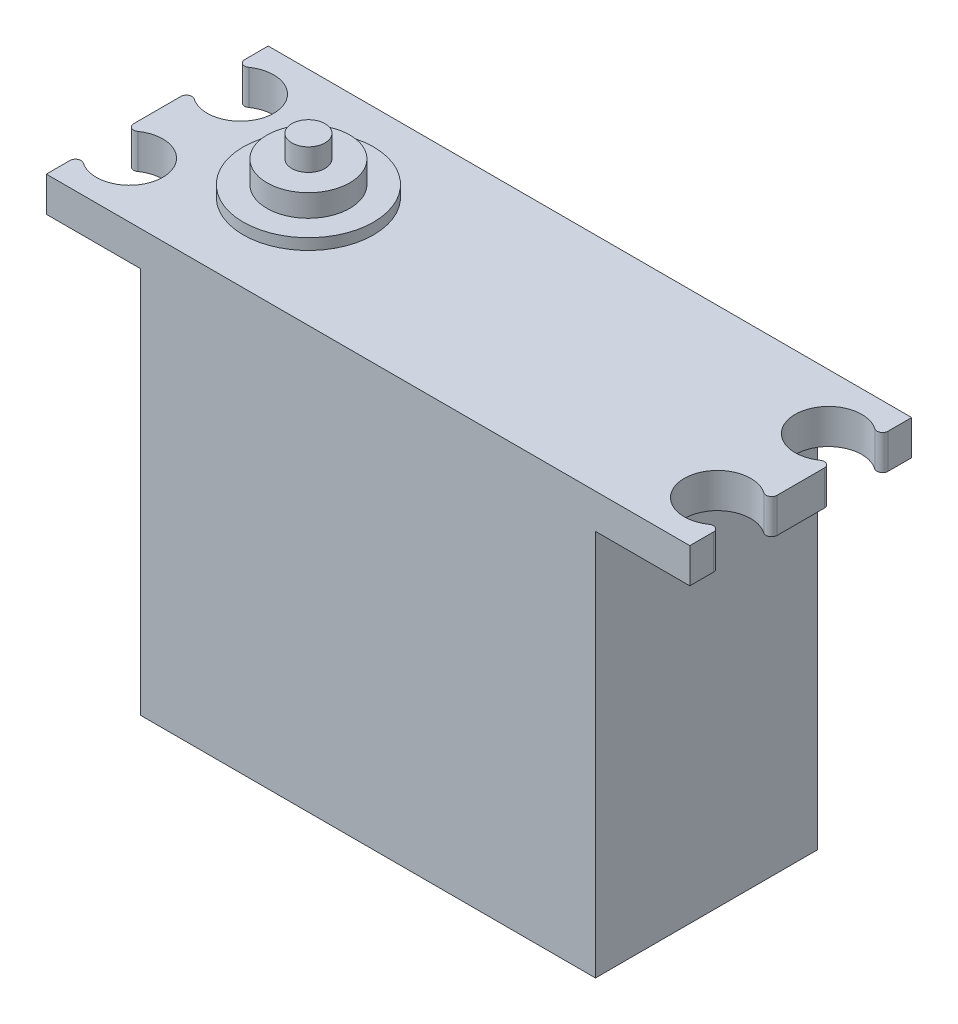
SolidWorks part; units mm, degrees
ref_plane "Front Plane" through (0, 0, 0) normal (0, 0, 1) x (1, 0, 0)
ref_plane "Top Plane" through (0, 0, 0) normal (0, 1, 0) x (1, 0, 0)
ref_plane "Right Plane" through (0, 0, 0) normal (1, 0, 0) x (0, 0, -1)
sketch "Sketch1" plane through (0, 0, 0) normal (0, 0, 1) x (1, 0, 0)
  line L0 (-29, 19) -> (29, 19)
  line L1 (20.5, -19) -> (-20.5, -19)
  line L2 (20.5, -19) -> (20.5, 15.8627)
  line L3 (20.5, 19) -> (-20.5, 19)
  line L4 (-20.5, -19) -> (-20.5, 15.8627)
  line L7 (-20.5, 15.8627) -> (-29, 15.8627)
  line L8 (29, 19) -> (29, 15.8627)
  line L9 (29, 15.8627) -> (20.5, 15.8627)
  line L10 (-29, 19) -> (-29, 15.8627)
  point P0 (0, 0)
  point P6 (0, 19)
  dimension "D1" = 41
  dimension "D2" = 38
extrude "Boss-Extrude1" add sketch "Sketch1" against normal blind 20 contours L0 L8 L9 L2 L1 L4 L7 L10
sketch "Sketch2" plane through (0, 19, 0) normal (0, 1, 0) x (1, 0, 0)
  line L0 (-29, 10) -> (31.146, 10) construction
  line L1 (-29, 20) -> (-29, 0) construction
  line L2 (0, 0) -> (0, 20) construction
  line L3 (-29, 0) -> (29, 0) construction
  line L4 (-29, 20) -> (29, 20) construction
  line L5 (29, 20) -> (29, 0) construction
  circle A0 centre (26.5, 5) radius 3
  circle A1 centre (26.5, 15) radius 3
  circle A2 centre (-26.5, 5) radius 3
  circle A3 centre (-26.5, 15) radius 3
  dimension "D1" = 6
  dimension "D2" = 2.5
  dimension "D3" = 10
extrude "Cut-Extrude2" cut sketch "Sketch2" against normal through all
fillet "Fillet1" radius 0.5 8 edges at (-29, 17.4314, -16.6583) (-29, 17.4314, -13.3417) (-29, 17.4314, -6.6583) (-29, 17.4314, -3.3417) (29, 17.4314, -13.3417) (29, 17.4314, -16.6583) (29, 17.4314, -6.6583) (29, 17.4314, -3.3417)
sketch "Sketch4" plane through (0, 19, 0) normal (0, 1, 0) x (1, 0, 0)
  line L0 (-29, 10) -> (29, 10) construction
  line L1 (-29, 12.1277) -> (-29, 7.8723) construction
  line L2 (29, 12.1277) -> (29, 7.8723) construction
  circle A0 centre (-15.3758, 10) radius 5.8721
extrude "Boss-Extrude2" add sketch "Sketch4" along normal blind 1
sketch "Sketch5" plane through (0, 20, 0) normal (0, 1, 0) x (1, 0, 0)
  circle A0 centre (-15.3758, 10) radius 3.7328
extrude "Boss-Extrude3" add sketch "Sketch5" along normal blind 2
sketch "Sketch8" plane through (0, 22, 0) normal (0, 1, 0) x (1, 0, 0)
  circle A0 centre (-15.3758, 10) radius 1.5
  dimension "D1" = 3
extrude "Boss-Extrude4" add sketch "Sketch8" along normal blind 2
